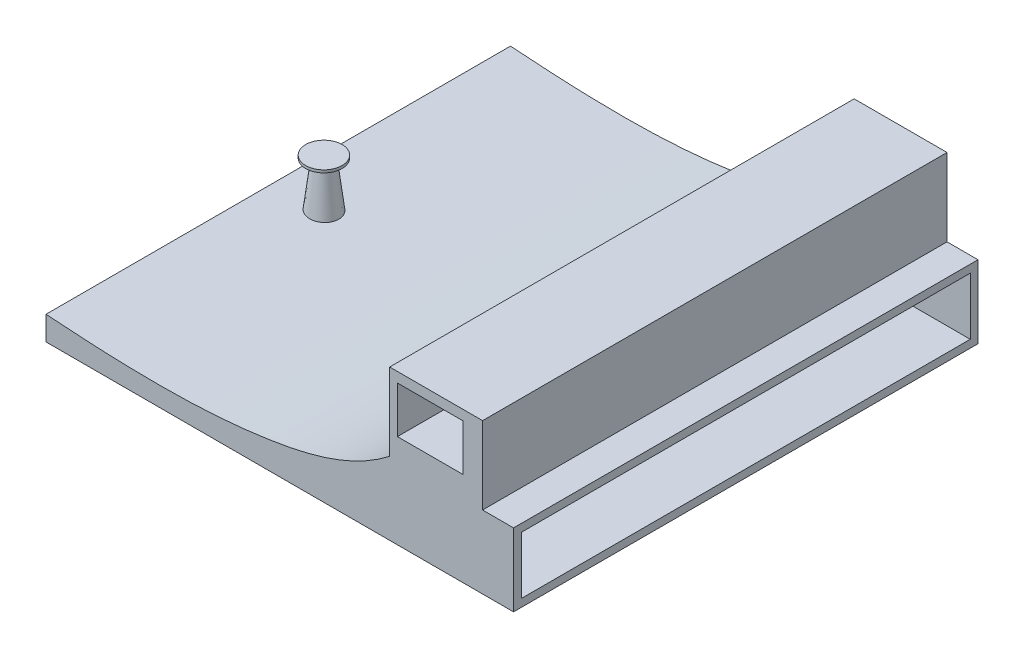
SolidWorks part; units mm, degrees
ref_plane "Front Plane" through (0, 0, 0) normal (0, 0, 1) x (1, 0, 0)
ref_plane "Top Plane" through (0, 0, 0) normal (0, 1, 0) x (1, 0, 0)
ref_plane "Right Plane" through (0, 0, 0) normal (1, 0, 0) x (0, 0, -1)
sketch "Sketch1" plane through (0, 0, 0) normal (0, 1, 0) x (1, 0, 0)
  line L1 (-24.7, 70) -> (24.7, 70)
  line L2 (-24.7, 70) -> (-24.7, -70)
  line L3 (-24.7, -70) -> (24.7, -70)
  line L4 (24.7, 70) -> (24.7, -70)
  line L5 (-24.7, 70) -> (24.7, -70) construction
  line L6 (-24.7, -70) -> (24.7, 70) construction
  point P0 (0, 0)
  dimension "D1" = 140
  dimension "D2" = 49.4
extrude "Boss-Extrude1" add sketch "Sketch1" along normal mid plane 20
sketch "Sketch5" plane through (0, 0, 0) normal (0, 0, 1) x (1, 0, 0)
  line L0 (0, 0) -> (24.7, 0) construction
  line L1 (24.7, 10) -> (24.7, -10) construction
  line L2 (24.7, 0) -> (24.7, -9.4)
  line L4 (-24.7, 10) -> (-24.7, -10) construction
  line L5 (-24.7, -9.4) -> (-24.7, -6.3)
  line L6 (-24.7, -9.4) -> (24.7, -9.4)
  line L7 (24.7, 0) -> (19.7, 0)
  spline S1 degree 3 poles (19.7, 0) (15.0434, -3.5747) (0.8183, -7.4778) (-14.2264, -7.0465) (-24.7, -6.3) knots 0 0 0 0 0.353407 1 1 1 1
  point P5 (8, -7.8508)
  point P11 (8, -5.2)
  dimension "D1" = 9.4
  dimension "D2" = 3.1
  dimension "D3" = 5
  dimension "D4" = 8
  dimension "D5" = 5.2
extrude "Boss-Extrude3" add sketch "Sketch5" along normal mid plane 60 separate body
combine bodies "Combine1" operation type common bodies to combine 102 103
sketch "Sketch8" plane through (0, 0, 0) normal (0, 0, 1) x (1, 0, 0)
  line L0 (-20.8, -7.364) -> (-20.0637, -1.3672)
  line L1 (-20.8, -7.364) -> (-18.8, -7.364)
  line L2 (-18.8, -0.8763) -> (-18.8, -7.364)
  line L4 (-20.3047, -0.8763) -> (-21.1508, -0.8763)
  line L5 (-18.8, -0.8763) -> (-18.8, -0.5359)
  line L6 (-18.8, -0.5359) -> (-21.1508, -0.5359)
  line L7 (-21.1508, -0.8763) -> (-21.1508, -0.5359)
  arc A1 (-20.3047, -0.8763) -> (-20.0637, -1.3672) centre (-20.56, -1.3062) cw
  dimension "D5" = 0.5
  dimension "D1" = 7
  dimension "D2" = 2.3508
  dimension "D3" = 2
revolve "Revolve2" add sketch "Sketch8" angle 360 about L2
sketch "Sketch25" plane through (24.7, 0, 0) normal (1, 0, 0) x (0, 0, -1)
  line L4 (-30, 0) -> (-30, -9.4)
  line L5 (30, 0) -> (-30, 0)
  line L6 (-30, 0) -> (-30, -9.4)
  line L7 (-30, -9.4) -> (30, -9.4)
  line L9 (30, 0) -> (-30, 0)
  line L15 (30, -9.4) -> (30, 0)
  line L16 (30, -9.4) -> (30, 0)
  line L17 (-30, -9.4) -> (30, -9.4)
  dimension "D1" = 0
extrude "Boss-Extrude4" add sketch "Sketch25" along normal blind 11 separate body
shell "Shell1" thickness 1 removed face at (35.7, -4.7, 0)
sketch "Sketch34" plane through (0, 0, 0) normal (0, 1, 0) x (1, 0, 0)
  line L0 (35.7, 30) -> (24.7, 30) construction
  line L22 (19.7, -30) -> (31.7, -30)
  line L23 (19.7, -30) -> (19.7, 30)
  line L24 (19.7, 30) -> (31.7, 30)
  line L25 (31.7, -30) -> (31.7, 30)
  dimension "D1" = 12
extrude "Boss-Extrude5" add sketch "Sketch34" along normal blind 10
sketch "Sketch38" plane through (0, 0, -30) normal (0, 0, -1) x (-1, 0, 0)
  line L1 (-29.1982, 8.7097) -> (-20.6982, 8.7097)
  line L2 (-29.1982, 8.7097) -> (-29.1982, 2.7097)
  line L3 (-29.1982, 2.7097) -> (-20.6982, 2.7097)
  line L4 (-20.6982, 8.7097) -> (-20.6982, 2.7097)
  line L5 (-29.1982, 8.7097) -> (-20.6982, 2.7097) construction
  line L6 (-29.1982, 2.7097) -> (-20.6982, 8.7097) construction
  point P0 (-24.9482, 5.7097)
  dimension "D1" = 6
  dimension "D2" = 8.5
  dimension "D3" = 20.6982
  dimension "D4" = 8.7097
extrude "Cut-Extrude3" cut sketch "Sketch38" against normal through all
